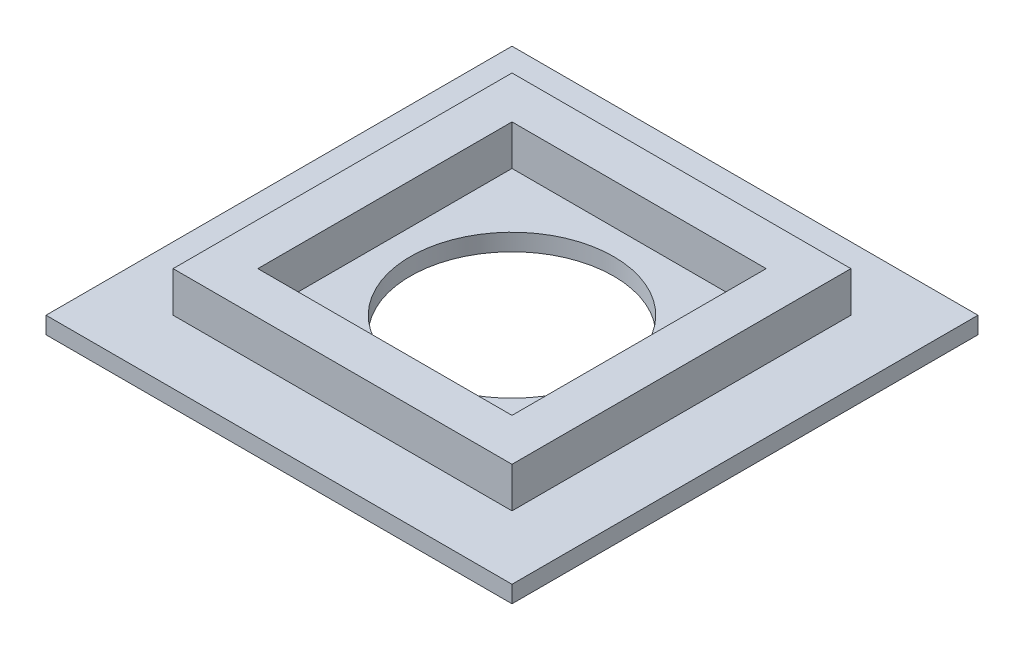
SolidWorks part; units mm, degrees
ref_plane "Front Plane" through (0, 0, 0) normal (0, 0, 1) x (1, 0, 0)
ref_plane "Top Plane" through (0, 0, 0) normal (0, 1, 0) x (1, 0, 0)
ref_plane "Right Plane" through (0, 0, 0) normal (1, 0, 0) x (0, 0, -1)
sketch "Sketch1" plane through (0, 0, 0) normal (0, 1, 0) x (1, 0, 0)
  line L1 (55, -55) -> (-55, -55)
  line L2 (55, -55) -> (55, 55)
  line L3 (55, 55) -> (-55, 55)
  line L4 (-55, -55) -> (-55, 55)
  line L5 (55, -55) -> (-55, 55) construction
  line L6 (55, 55) -> (-55, -55) construction
  point P0 (0, 0)
  dimension "D1" = 110
  dimension "D2" = 110
extrude "Boss-Extrude1" add sketch "Sketch1" against normal blind 4
sketch "Sketch2" plane through (0, 0, 0) normal (0, 1, 0) x (1, 0, 0)
  line L1 (40, 40) -> (-40, 40)
  line L2 (40, 40) -> (40, -40)
  line L3 (40, -40) -> (-40, -40)
  line L4 (-40, 40) -> (-40, -40)
  line L5 (40, 40) -> (-40, -40) construction
  line L6 (40, -40) -> (-40, 40) construction
  line L7 (30, 30) -> (-30, 30)
  line L8 (30, 30) -> (30, -30)
  line L9 (30, -30) -> (-30, -30)
  line L10 (-30, 30) -> (-30, -30)
  line L11 (30, 30) -> (-30, -30) construction
  line L12 (30, -30) -> (-30, 30) construction
  point P0 (0, 0)
  point P5 (0, 0)
  dimension "D1" = 80
  dimension "D2" = 80
  dimension "D3" = 60
  dimension "D4" = 60
extrude "Boss-Extrude2" add sketch "Sketch2" along normal blind 9.525
sketch "Sketch3" plane through (0, 0, 0) normal (0, 1, 0) x (1, 0, 0)
  circle A0 centre (0, 0) radius 24
  dimension "D1" = 48
extrude "Cut-Extrude1" cut sketch "Sketch3" against normal blind 20
ref_axis "Axis1" through (0, 21.2381, 0) along (0, -1, 0)
